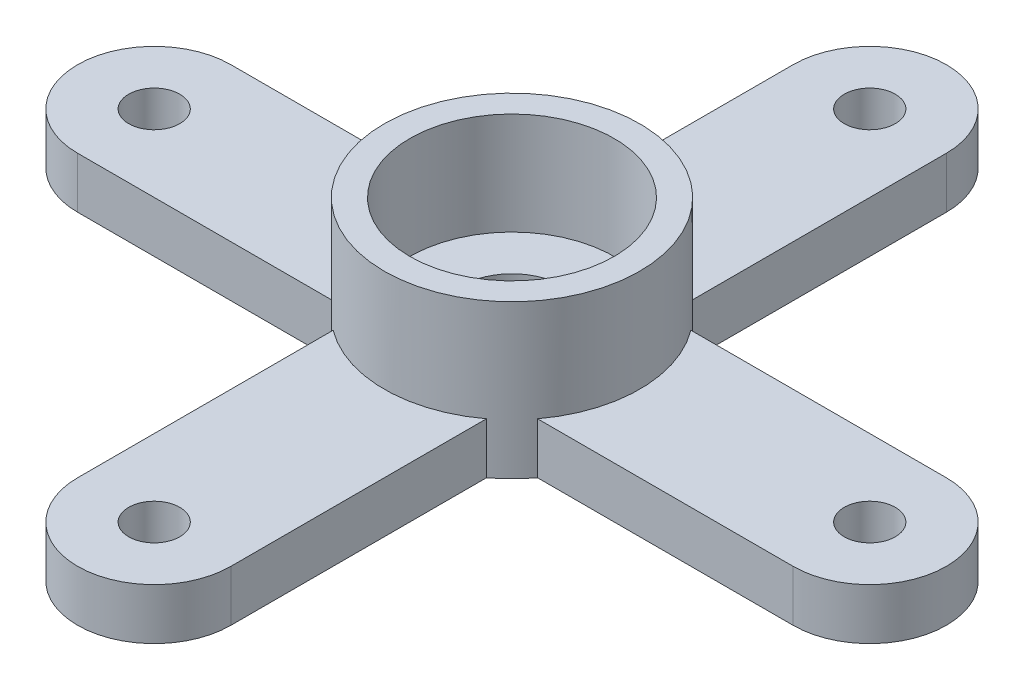
SolidWorks part; units mm, degrees
ref_plane "Front Plane" through (0, 0, 0) normal (0, 0, 1) x (1, 0, 0)
ref_plane "Top Plane" through (0, 0, 0) normal (0, 1, 0) x (1, 0, 0)
ref_plane "Right Plane" through (0, 0, 0) normal (1, 0, 0) x (0, 0, -1)
sketch "Sketch4" plane through (0, 0, 0) normal (0, 1, 0) x (1, 0, 0)
  line L0 (0, 0) -> (7, 0) construction
  line L1 (7, 1.5) -> (2, 1.5) construction
  line L2 (7, -1.5) -> (2, -1.5) construction
  line L3 (7, 1.5) -> (2, 1.5)
  line L4 (2, -1.5) -> (7, -1.5)
  line L5 (1.5, -7) -> (1.5, -2)
  line L6 (-1.5, -2) -> (-1.5, -7)
  line L7 (-7, -1.5) -> (-2, -1.5)
  line L8 (-2, 1.5) -> (-7, 1.5)
  line L9 (-1.5, 7) -> (-1.5, 2)
  line L10 (1.5, 2) -> (1.5, 7)
  circle A0 centre (0, 0) radius 2.5
  circle A1 centre (0, 0) radius 2
  circle A2 centre (7, 0) radius 1.5
  circle A3 centre (7, 0) radius 0.5
  circle A4 centre (0, 0) radius 1
  circle A5 centre (0, -7) radius 1.5
  circle A6 centre (0, -7) radius 0.5
  circle A7 centre (-7, 0) radius 1.5
  circle A8 centre (-7, 0) radius 0.5
  circle A9 centre (0, 7) radius 1.5
  circle A10 centre (0, 7) radius 0.5
  point P36 (0, 0)
  dimension "D1" = 4
extrude "Boss-Extrude1" add sketch "Sketch4" along normal blind 1 contours A9 A10 | A9 L9 A0 L10 | A2 L3 A0 L4 | A2 A3 | A0 A1 | A1 A4 | A7 A8 | A7 L7 A0 L8 | A5 L5 A0 L6 | A5 A6 region at (4.0943, 0, 0) region at (8.0307, 0, -1.0307) region at (2.3046, 0, -0.7682) region at (0, 0, -4.0943) region at (0, 0, -5.5424) region at (0, 0, 4.0943) region at (-4.0943, 0, 0) region at (0, 0, 8.4576) region at (-5.9693, 0, -1.0307) region at (-1.9434, 0, 0)
extrude "Boss-Extrude2" add sketch "Sketch4<3>" along normal blind 3 contours A0 | A1
sketch "Sketch4<3>" plane through (0, 0, 0) normal (0, 1, 0) x (1, 0, 0) same geometry as "Sketch4"
